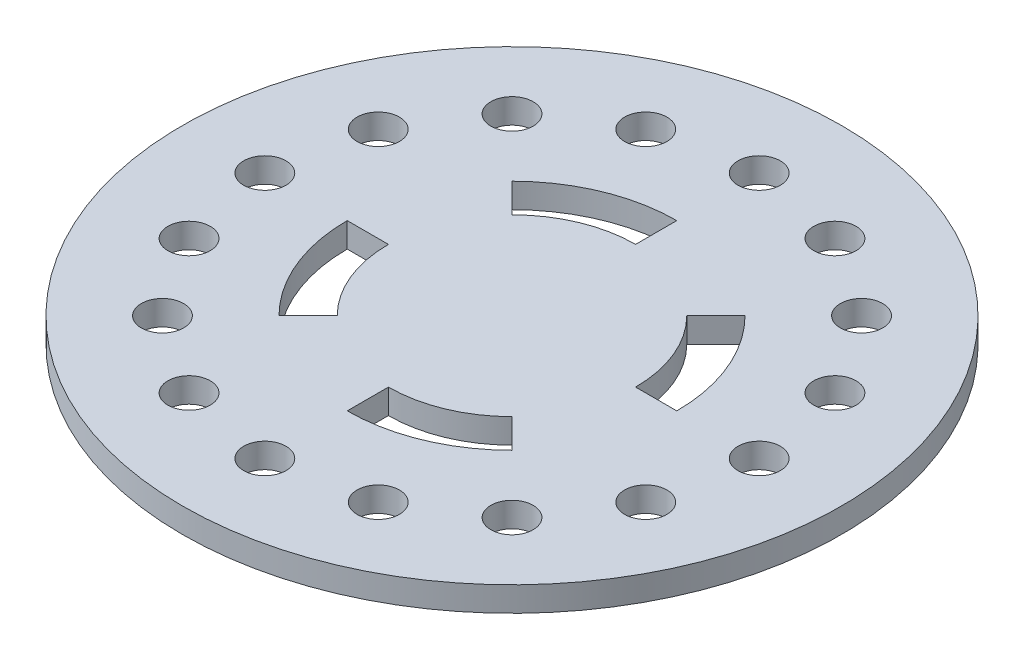
SolidWorks part; units mm, degrees
ref_plane "Front Plane" through (0, 0, 0) normal (0, 0, 1) x (1, 0, 0)
ref_plane "Top Plane" through (0, 0, 0) normal (0, 1, 0) x (1, 0, 0)
ref_plane "Right Plane" through (0, 0, 0) normal (1, 0, 0) x (0, 0, -1)
sketch "Sketch1" plane through (0, 0, 0) normal (0, 1, 0) x (1, 0, 0)
  circle A0 centre (0, 0) radius 50.8
  dimension "D1" = 101.6
extrude "Boss-Extrude1" add sketch "Sketch1" along normal blind 3.81
sketch "Sketch2" plane through (0, 3.81, 0) normal (0, 1, 0) x (1, 0, 0)
  line L0 (0, 0) -> (0, 25.4)
  line L1 (0, 0) -> (17.9605, 17.9605)
  line L2 (0, 0) -> (38.1, 0)
  line L3 (0, 0) -> (26.9408, -26.9408)
  line L4 (0, 0) -> (0, -38.1)
  line L5 (0, 0) -> (-26.9408, -26.9408)
  line L6 (0, 0) -> (-38.1, 0)
  line L7 (0, 0) -> (-26.9408, 26.9408)
  circle A0 centre (0, 0) radius 25.4
  circle A1 centre (0, 0) radius 19.05
  point P11 (-13.7464, 2.2911)
  dimension "D1" = 38.1
  dimension "D2" = 50.8
  dimension "D3" = 45
extrude "Cut-Extrude1" cut sketch "Sketch2" against normal through all contours A1 L0 A0 L7 | A1 L6 A0 L5 | A1 L4 A0 L3 | A1 L2 A0 L1 region at (-8.3446, 3.81, -20.1456) region at (20.1456, 3.81, -8.3446) region at (8.3446, 3.81, 20.1456) region at (-20.1456, 3.81, 8.3446)
sketch "Sketch3" plane through (0, 3.81, 0) normal (0, 1, 0) x (1, 0, 0)
  line L0 (0, 0) -> (0, 25.4) construction
  line L1 (0, 0) -> (17.9605, 17.9605) construction
  line L2 (14.5802, 35.1998) -> (0, 0) construction
  circle A0 centre (14.5802, 35.1998) radius 3.2639
  circle A1 centre (26.9408, 26.9408) radius 3.2639
  circle A2 centre (35.1998, 14.5802) radius 3.2639
  circle A3 centre (38.1, 0) radius 3.2639
  circle A4 centre (35.1998, -14.5802) radius 3.2639
  circle A5 centre (26.9408, -26.9408) radius 3.2639
  circle A6 centre (14.5802, -35.1998) radius 3.2639
  circle A7 centre (0, -38.1) radius 3.2639
  circle A8 centre (-14.5802, -35.1998) radius 3.2639
  circle A9 centre (-26.9408, -26.9408) radius 3.2639
  circle A10 centre (-35.1998, -14.5802) radius 3.2639
  circle A11 centre (-38.1, 0) radius 3.2639
  circle A12 centre (-35.1998, 14.5802) radius 3.2639
  circle A13 centre (-26.9408, 26.9408) radius 3.2639
  circle A14 centre (-14.5802, 35.1998) radius 3.2639
  circle A15 centre (0, 38.1) radius 3.2639
  point P17 (0, 0)
  dimension "D1" = 6.5278
  dimension "D2" = 22.5
  dimension "D3" = 38.1
  dimension "D4" = 16
extrude "Cut-Extrude2" cut sketch "Sketch3" against normal through all contours A0 | A1 | A2 | A4 | A5 | A6 | A7 | A8 | A9 | A10 | A11 | A12 | A13 | A14 | A15 | A3 region at (14.5802, 3.81, -35.1998) region at (26.9408, 3.81, -26.9408) region at (35.1998, 3.81, -14.5802) region at (35.1998, 3.81, 14.5802) region at (26.9408, 3.81, 26.9408) region at (14.5802, 3.81, 35.1998) region at (0, 3.81, 38.1) region at (-14.5802, 3.81, 35.1998) region at (-26.9408, 3.81, 26.9408) region at (-35.1998, 3.81, 14.5802) region at (-38.1, 3.81, 0) region at (-35.1998, 3.81, -14.5802) region at (-26.9408, 3.81, -26.9408) region at (-14.5802, 3.81, -35.1998) region at (0, 3.81, -38.1)
